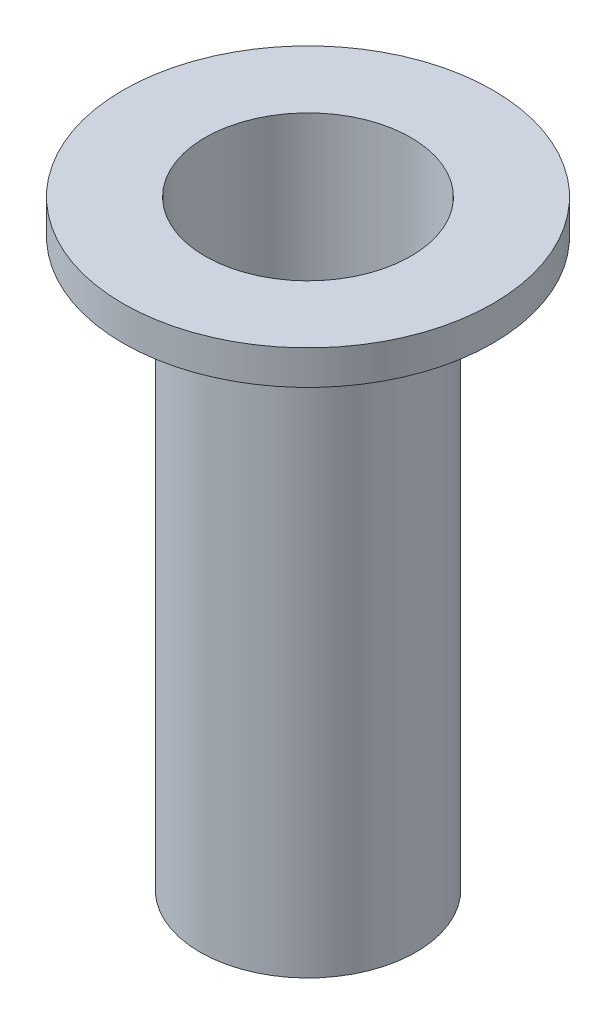
SolidWorks part; units mm, degrees
material "ABS PC"
ref_plane "Front Plane" through (0, 0, 0) normal (0, 0, 1) x (1, 0, 0)
ref_plane "Top Plane" through (0, 0, 0) normal (0, 1, 0) x (1, 0, 0)
ref_plane "Right Plane" through (0, 0, 0) normal (1, 0, 0) x (0, 0, -1)
sketch "Sketch1" plane through (0, 0, 0) normal (0, 1, 0) x (1, 0, 0)
  circle A0 centre (0, 0) radius 8.001
  dimension "D1" = 16.002
extrude "Boss-Extrude1" add sketch "Sketch1" along normal blind 44.45
sketch "Sketch2" plane through (0, 44.45, 0) normal (0, 1, 0) x (1, 0, 0)
  circle A0 centre (0, 0) radius 7.62
  dimension "D1" = 15.24
extrude "Cut-Extrude1" cut sketch "Sketch2" against normal blind 43.18
sketch "Sketch3" plane through (0, 1.27, 0) normal (0, 1, 0) x (1, 0, 0)
  circle A0 centre (0, 0) radius 6.35
  dimension "D1" = 12.7
extrude "Cut-Extrude2" cut sketch "Sketch3" against normal blind 1.27
chamfer "Chamfer2" distance 1.27 angle 45 1 edges at (0, 0, 6.35)
sketch "Sketch5" plane through (0, 0, 0) normal (0, 0, 1) x (1, 0, 0)
  line L0 (8.001, 44.45) -> (13.698, 44.45)
  line L1 (13.698, 44.45) -> (13.698, 41.91)
  line L3 (8.001, 0) -> (8.001, 44.45) construction
  line L4 (8.001, 40.9903) -> (8.001, 44.45)
  arc A0 (13.698, 41.91) -> (8.001, 40.9903) centre (13.698, 23.8054) ccw
  dimension "D1" = 2.54
ref_axis "Axis1" through (0, 1.27, 0) along (0, 1, 0)
revolve "Revolve1" add sketch "Sketch5" angle 360 about axis through (0, 1.27, 0) along (0, 1, 0)
